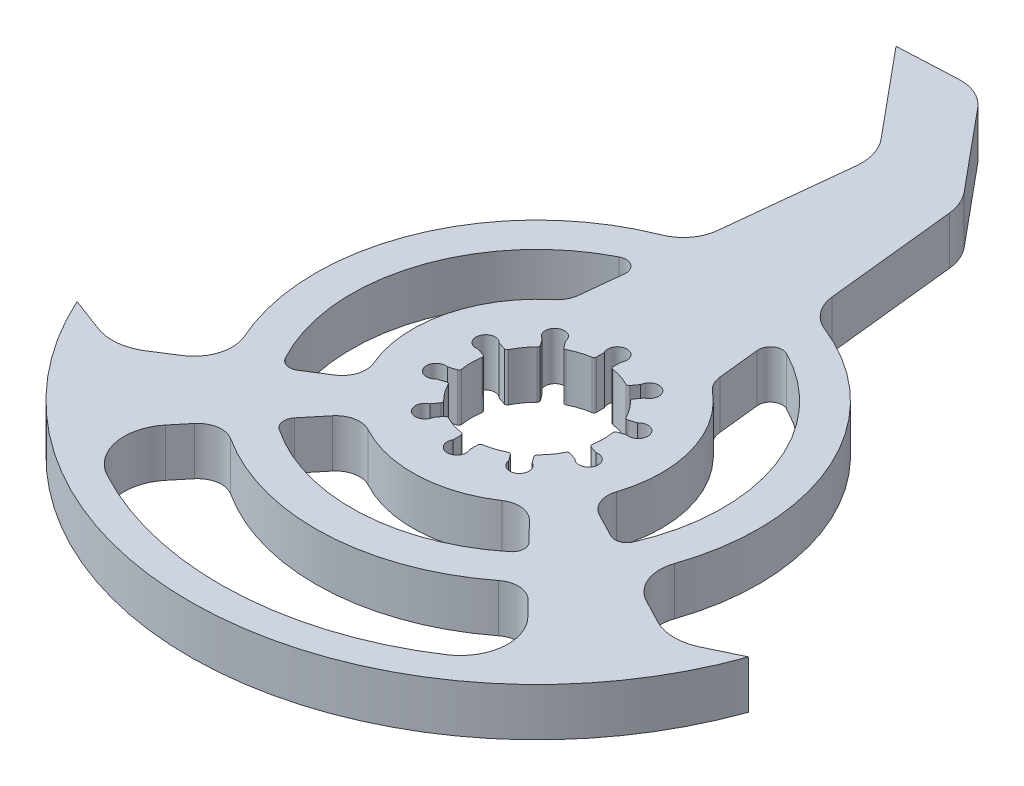
SolidWorks part; units mm, degrees
material "AISI Type A2 Tool Steel"
ref_plane "Front Plane" through (0, 0, 0) normal (0, 0, 1) x (1, 0, 0)
ref_plane "Top Plane" through (0, 0, 0) normal (0, 1, 0) x (1, 0, 0)
ref_plane "Right Plane" through (0, 0, 0) normal (1, 0, 0) x (0, 0, -1)
other "Center of Mass"
other "Bounding Box"
ref_plane "Default Plane" through (0, 2.286, 19.05) normal (0, -1, 0) x (-1, 0, 0)
sketch "Sketch1" plane through (0, 0, 0) normal (0, 1, 0) x (1, 0, 0)
  circle A0 centre (0, 0) radius 133.35 construction
  circle A1 centre (0, 0) radius 33.02
  circle A2 centre (0, 0) radius 17.4625
  dimension "D1" = 266.7
  dimension "D2" = 66.04
  dimension "D3" = 34.925
extrude "Boss-Extrude1" add sketch "Sketch1" along normal mid plane 12.7
sketch "Sketch2" plane through (0, 6.35, 0) normal (0, 1, 0) x (1, 0, 0)
  line L0 (-11.1125, 101.6) -> (-19.05, 26.9707)
  line L1 (19.05, 26.9707) -> (11.1125, 101.6)
  line L4 (0, 0) -> (0, 133.35) construction
  line L5 (-11.1125, 101.6) -> (0, 101.6) construction
  line L6 (0, 101.6) -> (11.1125, 101.6) construction
  line L7 (-33.8496, 128.9823) -> (0, 0) construction
  line L8 (-33.8496, 128.9823) -> (120.5643, -56.9779) construction
  line L9 (-33.8496, 128.9823) -> (-11.1125, 101.6)
  line L11 (-33.8496, 128.9823) -> (-17.9923, 129.7314)
  line L13 (-29.318, 130.1715) -> (44478.1204, 11810.5452) construction
  line L14 (11.1125, 101.6) -> (-8.9277, 125.7344)
  circle A0 centre (0, 0) radius 133.35 construction
  circle A1 centre (0, 0) radius 133.35 construction
  circle A5 centre (0, 0) radius 33.02
  arc A6 (19.05, 26.9707) -> (-19.05, 26.9707) centre (0, 0) ccw
  arc A7 (-19.05, 26.9707) -> (19.05, 26.9707) centre (0, 0) ccw construction
  arc A8 (-17.9923, 129.7314) -> (-8.9277, 125.7344) centre (-17.4684, 118.6425) cw
  point P6 (-3.4399, 122.4629)
  point P14 (-3.468, 123.4258)
  point P16 (-11.1125, 126.7774)
  dimension "D3" = 12
  dimension "D4" = 38.1
  dimension "D5" = 15.875
  dimension "D6" = 22.225
  dimension "D1" = 25
  dimension "D7" = 31.75
  dimension "D2" = 0
extrude "Boss-Extrude2" add sketch "Sketch2" against normal through all
sketch "Sketch3" plane through (0, 6.35, 0) normal (0, 1, 0) x (1, 0, 0)
  line L2 (1.4403, -32.9886) -> (4.0163, -91.9874) construction
  line L3 (-83.7847, -38.1829) -> (-68.7555, -43.8021)
  line L4 (-27.8488, -17.7416) -> (0, 0) construction
  line L5 (0, 0) -> (29.2891, -15.2469) construction
  line L6 (-68.7555, -43.8021) -> (-27.8488, -17.7416)
  line L7 (29.2891, -15.2469) -> (72.3114, -37.643)
  line L8 (72.3114, -37.643) -> (86.7937, -30.7353)
  line L9 (-81.7832, -37.2708) -> (44329.4081, 20202.0751) construction
  line L10 (0, -2.7022) -> (0, -50002.7022) construction
  arc A0 (-83.7847, -38.1829) -> (86.7937, -30.7353) centre (0, 0) ccw
  circle A1 centre (0, 0) radius 33.02 construction
  arc A3 (-27.8488, -17.7416) -> (29.2891, -15.2469) centre (0, 0) ccw
  point P13 (4.0163, -91.9874)
  dimension "D2" = 92.075
  dimension "D1" = 45
  dimension "D3" = 120
  dimension "D4" = 8
  dimension "D5" = 2.5
extrude "Boss-Extrude3" add sketch "Sketch3" against normal through all
sketch "Sketch5" plane through (0, 6.35, 0) normal (0, 1, 0) x (1, 0, 0)
  line L0 (0, 17.4625) -> (0, 21.2725) construction
  line L2 (-2.2225, 17.3205) -> (2.2225, 17.3205)
  line L3 (-2.2225, 17.3205) -> (-2.2225, 20.0168)
  line L5 (2.2225, 17.3205) -> (2.2225, 20.0168)
  arc A0 (2.2225, 20.0168) -> (-2.2225, 20.0168) centre (0, 21.2725) ccw
  circle A1 centre (0, 0) radius 17.4625 construction
  circle A2 centre (0, 21.2725) radius 4.5847 construction
  dimension "D2" = 5.1054
  dimension "D4" = 9.1694
  dimension "D1" = 3.81
  dimension "D3" = 4.445
extrude "Cut-Extrude2" cut sketch "Sketch5" against normal through all
pattern_circular "CirPattern1" count 10 over 360 about axis through (0, 6.35, 0) along (0, -1, 0) of "Cut-Extrude2"
sketch "Sketch6" plane through (0, 6.35, 0) normal (0, 1, 0) x (1, 0, 0)
  circle A0 centre (0, 0) radius 17.526
  arc A1 (-11.9788, 12.7062) -> (-15.786, 7.466) centre (0, 0) ccw construction
  dimension "D1" = 0.0635
extrude "Cut-Extrude3" cut sketch "Sketch6" against normal through all
sketch "Sketch7" plane through (0, 6.35, 0) normal (0, 1, 0) x (1, 0, 0)
  line L0 (-52.6456, -65.6157) -> (-20.1317, -26.1732)
  line L1 (22.3362, -24.319) -> (58.164, -60.7777)
  line L6 (0, 0) -> (3.6695, -84.0447) construction
  line L7 (3.6695, -84.0447) -> (4.0163, -91.9874) construction
  line L8 (-27.8488, -17.7416) -> (-20.1317, -26.1732) construction
  line L9 (-27.8488, -17.7416) -> (-68.7555, -43.8021) construction
  arc A0 (-20.1317, -26.1732) -> (22.3362, -24.319) centre (0, 0) ccw
  arc A1 (-52.6456, -65.6157) -> (58.164, -60.7777) centre (0, 0) ccw
  arc A3 (-83.7847, -38.1829) -> (86.7937, -30.7353) centre (0, 0) ccw construction
  arc A4 (29.2891, -15.2469) -> (19.05, 26.9707) centre (0, 0) ccw construction
  dimension "D1" = 11.43
  dimension "D2" = 7.9502
  dimension "D3" = 18
extrude "Cut-Extrude4" cut sketch "Sketch7" against normal through all
sketch "Sketch8" plane through (0, 6.35, 0) normal (0, 1, 0) x (1, 0, 0)
  circle A0 centre (0, 0) radius 49.2125
  circle A1 centre (0, 0) radius 58.7375
  dimension "D1" = 9.525
  dimension "D2" = 117.475
extrude "Boss-Extrude4" add sketch "Sketch8" against normal through all
sketch "Sketch11" plane through (0, 6.35, 0) normal (0, 1, 0) x (1, 0, 0)
  line L0 (-6.9918, 32.2713) -> (-5.2194, 48.9349)
  line L1 (5.2194, 48.9349) -> (6.9918, 32.2713)
  line L3 (-17.0069, 46.1805) -> (-19.05, 26.9707) construction
  line L4 (19.05, 26.9707) -> (17.0069, 46.1805) construction
  line L5 (-6.1056, 40.6031) -> (-17.4715, 41.812) construction
  line L6 (6.1056, 40.6031) -> (17.4715, 41.812) construction
  arc A0 (-6.9918, 32.2713) -> (6.9918, 32.2713) centre (0, 0) cw
  arc A1 (-5.2194, 48.9349) -> (5.2194, 48.9349) centre (0, 0) cw
  arc A2 (-19.05, 26.9707) -> (-27.8488, -17.7416) centre (0, 0) ccw construction
  arc A3 (-17.0069, 46.1805) -> (-41.5054, -26.4419) centre (0, 0) ccw construction
  dimension "D1" = 11.43
extrude "Cut-Extrude6" [suppressed] cut sketch "Sketch11" against normal through all
fillet "Fillet1" radius 6.35 8 edges at (19.05, 0, -26.9707) (-19.05, 0, -26.9707) (22.3362, 0, 24.319) (-20.1317, 0, 26.1732) (40.3676, 0, 42.6679) (-36.4953, 0, 46.0238) (29.2891, 0, 15.2469) (-27.8488, 0, 17.7416)
fillet "Fillet6" radius 0.635 20 edges at (-12.0164, 0, -12.758) (-15.8469, 0, -7.4858) (-17.2204, 0, -3.2584) (-17.2204, 0, 3.2584) (-15.8469, 0, 7.4858) (-12.0164, 0, 12.758) (-8.4203, 0, 15.3707) (-2.2225, 0, 17.3845) (2.2225, 0, 17.3845) (8.4203, 0, 15.3707) (12.0164, 0, 12.758) (15.8469, 0, 7.4858) (17.2204, 0, 3.2584) (17.2204, 0, -3.2584) (15.8469, 0, -7.4858) (12.0164, 0, -12.758) (8.4203, 0, -15.3707) (2.2225, 0, -17.3845) (-2.2225, 0, -17.3845) (-8.4203, 0, -15.3707)
fillet "Fillet7" radius 3.175 6 edges at (-30.4353, 0, 38.6725) (33.69, 0, 35.8727) (-17.0069, 0, -46.1805) (17.0069, 0, -46.1805) (43.652, 0, 22.7238) (-41.5054, 0, 26.4419)
fillet "Fillet8" radius 10.16 4 edges at (-15.9047, 0, -56.5432) (15.9047, 0, -56.5432) (52.1008, 0, 27.122) (-49.5387, 0, 31.5596)
fillet "Fillet9" [suppressed] radius 3.175
sketch "Sketch12" plane through (0, -6.35, 0) normal (0, -1, 0) x (1, 0, 0)
  line L0 (-58.7375, 0) -> (-53.975, 0) construction
  line L1 (-53.975, 0) -> (-49.2125, 0) construction
  circle A0 centre (0, 0) radius 53.975
  arc A1 (-53.6511, 23.9094) -> (-21.5869, -54.6269) centre (0, 0) ccw construction
  arc A2 (-43.2302, 23.5165) -> (-22.1704, -43.9357) centre (0, 0) ccw construction
fillet "Fillet10" radius 12.7 4 edges at (72.3114, 0, 37.643) (-68.7555, 0, 43.8021) (58.164, 0, 60.7777) (-52.6456, 0, 65.6157)
fillet "Fillet11" radius 12.7 2 edges at (-11.1125, 0, -101.6) (11.1125, 0, -101.6)
equation "\"Unit Measure\"= \"BoundingVolume\" / \"Thickness\"'in^2"
